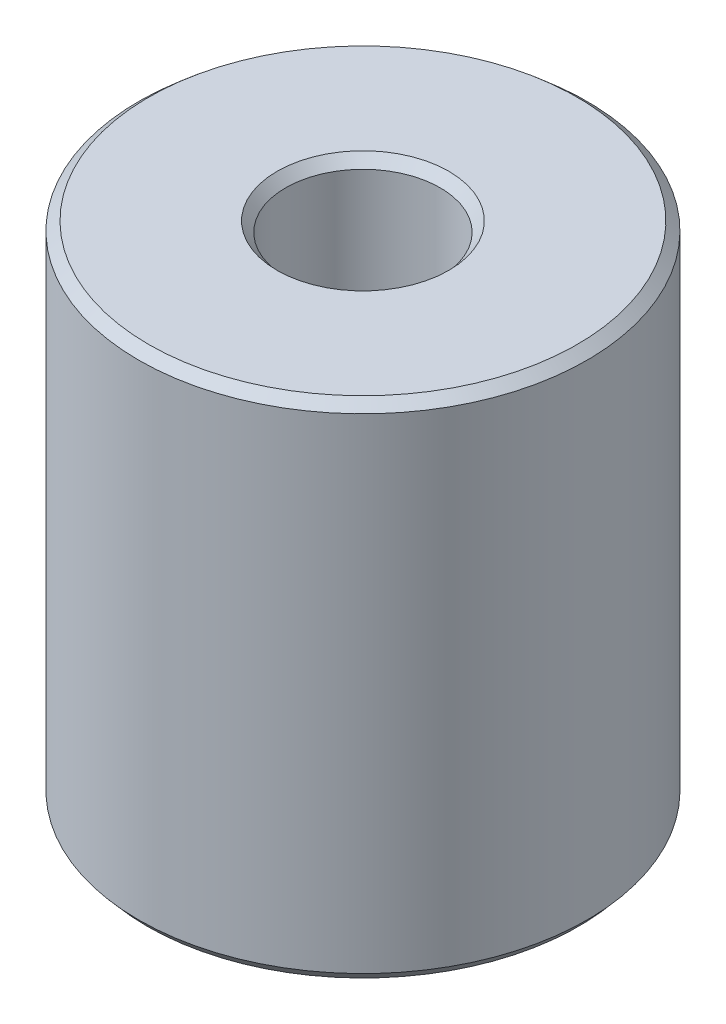
SolidWorks part; units mm, degrees
ref_plane "Front Plane" through (0, 0, 0) normal (0, 0, 1) x (1, 0, 0)
ref_plane "Top Plane" through (0, 0, 0) normal (0, 1, 0) x (1, 0, 0)
ref_plane "Right Plane" through (0, 0, 0) normal (1, 0, 0) x (0, 0, -1)
sketch "Sketch1" plane through (0, 0, 0) normal (0, 1, 0) x (1, 0, 0)
  circle A0 centre (0, 0) radius 7.5
  dimension "SLEEVE_OD" = 15
extrude "Boss-Extrude1" add sketch "Sketch1" along normal blind 16.8402
sketch "Sketch2" plane through (0, 0, 0) normal (0, 1, 0) x (1, 0, 0)
  circle A0 centre (0, 0) radius 2.5843
  dimension "BORE_D" = 5.1687
extrude "Cut-Extrude1" cut sketch "Sketch2" along normal through all
chamfer "Chamfer1" distance 0.2885 angle 49.076 4 edges at (0, 16.8402, 2.5843) (0, 0, 2.5843) (0, 0, 7.5) (0, 16.8402, 7.5) first distance on face at (0, 16.8402, 2.5843) first distance on face at (0, 0, 2.5843) first distance on face at (0, 16.8402, 7.5)
